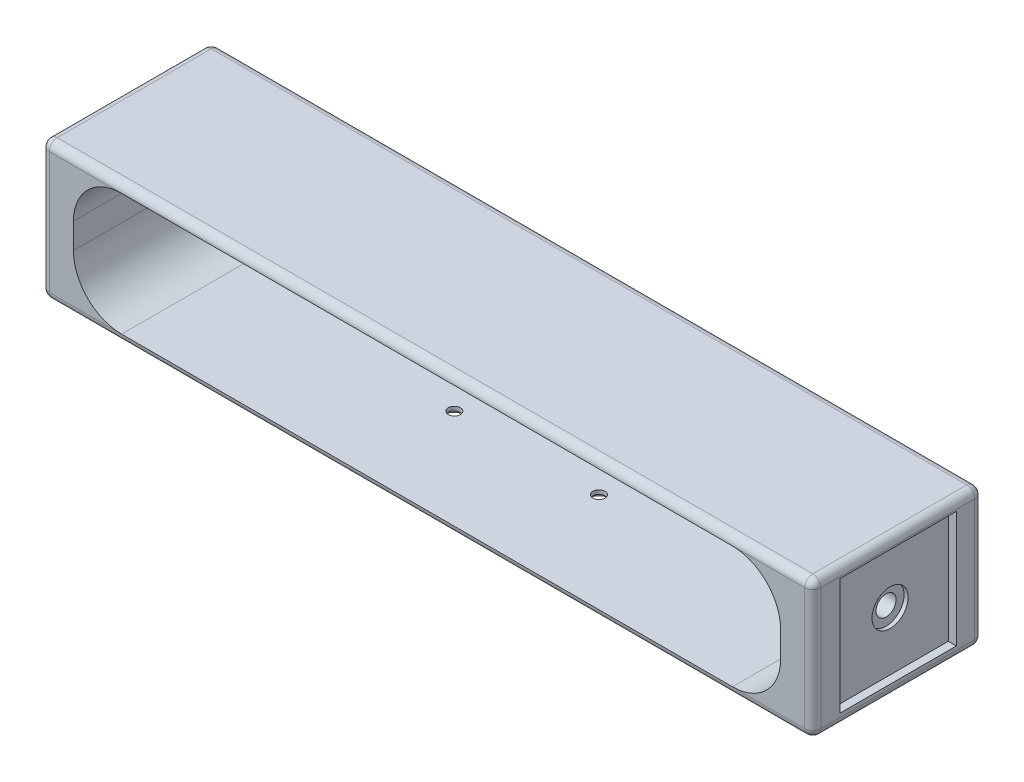
SolidWorks part; units mm, degrees
ref_plane "Front Plane" through (0, 0, 0) normal (0, 0, 1) x (1, 0, 0)
ref_plane "Top Plane" through (0, 0, 0) normal (0, 1, 0) x (1, 0, 0)
ref_plane "Right Plane" through (0, 0, 0) normal (1, 0, 0) x (0, 0, -1)
sketch "Sketch1" plane through (0, 0, 0) normal (0, 1, 0) x (1, 0, 0)
  line L1 (-96, 21.15) -> (96, 21.15)
  line L2 (-96, 21.15) -> (-96, -21.15)
  line L3 (-96, -21.15) -> (96, -21.15)
  line L4 (96, 21.15) -> (96, -21.15)
  line L5 (-96, 21.15) -> (96, -21.15) construction
  line L6 (-96, -21.15) -> (96, 21.15) construction
  point P0 (0, 0)
  dimension "D1" = 42.3
  dimension "D2" = 192
extrude "Boss-Extrude1" add sketch "Sketch1" along normal blind 2
sketch "Sketch2" plane through (0, 2, 0) normal (0, 1, 0) x (1, 0, 0)
  line L0 (-96, -21.15) -> (96, -21.15) construction
  line L1 (-96, -21.15) -> (-88, -21.15)
  line L2 (-96, -21.15) -> (-96, 21.15)
  line L3 (-96, 21.15) -> (-88, 21.15)
  line L4 (-88, -21.15) -> (-88, 21.15)
  line L5 (96, 21.15) -> (88, 21.15)
  line L6 (96, 21.15) -> (96, -21.15)
  line L7 (96, -21.15) -> (88, -21.15)
  line L8 (88, 21.15) -> (88, -21.15)
  line L10 (88, 21.15) -> (-88, 21.15)
  line L11 (88, 21.15) -> (88, 19.15)
  line L12 (88, 19.15) -> (-88, 19.15)
  line L13 (-88, 21.15) -> (-88, 19.15)
  line M5 (96, -21.15) -> (96, 21.15)
  line M6 (96, 21.15) -> (-96, 21.15)
  line M7 (-96, 21.15) -> (-96, -21.15)
  line M8 (-96, -21.15) -> (96, -21.15)
  dimension "D1" = 8
  dimension "D2" = 8
  dimension "D3" = 2
extrude "Boss-Extrude2" add sketch "Sketch2" along normal blind 30.35 contours L4 M8 M6 M7 | L12 L8 L4 M6 | L8 M6 M8 M5 region at (-92, 2, 0) region at (0, 2, -20.15) region at (92, 2, 0)
sketch "Sketch3" plane through (0, 32.35, 0) normal (0, 1, 0) x (1, 0, 0)
  line L1 (-96, 21.15) -> (96, 21.15)
  line L2 (-96, 21.15) -> (-96, -21.15)
  line L3 (-96, -21.15) -> (96, -21.15)
  line L4 (96, 21.15) -> (96, -21.15)
extrude "Boss-Extrude3" add sketch "Sketch3" along normal blind 2
fillet "Fillet1" radius 12 1 edges at (-88, 32.35, 1)
fillet "Fillet2" radius 12 1 edges at (-88, 2, 1)
fillet "Fillet3" radius 12 1 edges at (88, 32.35, 1)
fillet "Fillet4" radius 12 1 edges at (88, 2, 1)
sketch "Sketch4" plane through (0, 0, -19.15) normal (0, 0, 1) x (1, 0, 0)
  line L0 (-88, 20.35) -> (-88, 14)
  line L1 (-88, 14) -> (-76, 2)
  line L2 (-76, 2) -> (-26, 2)
  line L3 (76, 2) -> (-76, 2) construction
  line L4 (-26, 2) -> (-26, 32.35)
  line L5 (76, 32.35) -> (-76, 32.35) construction
  line L6 (-26, 32.35) -> (-76, 32.35)
  line L7 (-76, 32.35) -> (-88, 20.35)
  arc A0 (-76, 32.35) -> (-88, 20.35) centre (-76, 20.35) ccw
  arc A1 (-88, 14) -> (-76, 2) centre (-76, 14) ccw
  line M7 (-76, 2) -> (76, 2)
  line M11 (76, 32.35) -> (-76, 32.35)
  arc M12 (-76, 32.35) -> (-88, 20.35) centre (-76, 20.35) ccw
  line M13 (-88, 20.35) -> (-88, 14)
  arc M14 (-88, 14) -> (-76, 2) centre (-76, 14) ccw
  dimension "D1" = 50
  dimension "D2" = 50
extrude "Cut-Extrude1" cut sketch "Sketch4" against normal blind 2 contours L7 M12 | L1 M14 | L7 L1 L4 M11 M13 M7 region at (-54.7626, 17.175, -19.15) region at (-83.0078, 27.3578, -19.15) region at (-83.0078, 6.9922, -19.15)
sketch "Sketch5" plane through (0, 0, -19.15) normal (0, 0, 1) x (1, 0, 0)
  line L0 (76, 32.35) -> (26, 32.35)
  line L1 (76, 32.35) -> (-26, 32.35) construction
  line L2 (26, 32.35) -> (26, 2)
  line L3 (76, 2) -> (-26, 2) construction
  line L4 (26, 2) -> (76, 2)
  line L5 (76, 2) -> (88, 14)
  line L6 (88, 14) -> (88, 20.35)
  line L7 (88, 20.35) -> (76, 32.35)
  arc A0 (76, 2) -> (88, 14) centre (76, 14) ccw construction
  arc A1 (76, 32.35) -> (88, 20.35) centre (76, 20.35) cw
  arc A2 (88, 14) -> (76, 2) centre (76, 14) cw
  line M8 (-26, 2) -> (76, 2)
  arc M9 (76, 2) -> (88, 14) centre (76, 14) ccw
  line M10 (88, 14) -> (88, 20.35)
  arc M11 (88, 20.35) -> (76, 32.35) centre (76, 20.35) ccw
  line M12 (76, 32.35) -> (-26, 32.35)
  dimension "D1" = 50
extrude "Cut-Extrude2" cut sketch "Sketch5" against normal blind 2 contours L7 L2 L5 M10 M12 M8 | L7 M11 | L5 M9 region at (54.7626, 17.175, -19.15) region at (83.0078, 27.3578, -19.15) region at (83.0078, 6.9922, -19.15)
sketch "Sketch6" plane through (-96, 0, 0) normal (-1, 0, 0) x (0, 0, 1)
  circle A0 centre (0, 17.175) radius 4
extrude "Boss-Extrude5" add sketch "Sketch6" along normal blind 6
sketch "Sketch7" plane through (-102, 0, 0) normal (-1, 0, 0) x (0, 0, 1)
  circle A0 centre (0, 17.175) radius 2.25
  dimension "D1" = 4.5
extrude "Cut-Extrude3" cut sketch "Sketch7" against normal blind 10
sketch "Sketch8" plane through (-102, 0, 0) normal (-1, 0, 0) x (0, 0, 1)
  line L1 (-0.75, 21.7837) -> (0.75, 21.7837)
  line L2 (-0.75, 21.7837) -> (-0.75, 12.5663)
  line L3 (-0.75, 12.5663) -> (0.75, 12.5663)
  line L4 (0.75, 21.7837) -> (0.75, 12.5663)
  line L5 (-0.75, 21.7837) -> (0.75, 12.5663) construction
  line L6 (-0.75, 12.5663) -> (0.75, 21.7837) construction
  point P0 (0, 17.175)
  dimension "D1" = 1.5
extrude "Cut-Extrude4" cut sketch "Sketch8" against normal blind 6
sketch "Sketch10" plane through (0, 0, 0) normal (0, -1, 0) x (1, 0, 0)
  circle A0 centre (-18.0029, -3.6557) radius 1.5
  circle A1 centre (17.9971, -3.6557) radius 1.5
  dimension "D1" = 3
  dimension "D2" = 3
extrude "Cut-Extrude9" cut sketch "Sketch10" against normal blind 6
fillet "Fillet5" radius 2 1 edges at (0, 0, -21.15)
fillet "Fillet6" radius 2 1 edges at (0, 34.35, -21.15)
fillet "Fillet9" radius 2 5 edges at (96, 34.35, 1) (96, 33.7642, -20.5642) (96, 0, 1) (96, 0.5858, -20.5642) (96, 17.175, -21.15)
fillet "Fillet10" radius 2 5 edges at (-96, 34.35, 1) (-96, 33.7642, -20.5642) (-96, 0, 1) (-96, 0.5858, -20.5642) (-96, 17.175, -21.15)
fillet "Fillet11" radius 2 8 edges at (-95.4142, 33.7642, 21.15) (-96, 17.175, 21.15) (-95.4142, 0.5858, 21.15) (0, 0, 21.15) (95.4142, 0.5858, 21.15) (96, 17.175, 21.15) (95.4142, 33.7642, 21.15) (0, 34.35, 21.15)
fillet "Fillet14" radius 1 1 edges at (-102, 17.175, 4)
fillet "Fillet15" radius 1 1 edges at (-102, 17.175, -4)
sketch "Sketch11" plane through (0, 0, 0) normal (0, -1, 0) x (-1, 0, 0)
  circle A0 centre (18.0029, 3.6557) radius 2.5
  circle A1 centre (-17.9971, 3.6557) radius 2.5
  dimension "D1" = 5
  dimension "D2" = 5
extrude "Cut-Extrude11" cut sketch "Sketch11" against normal blind 1
sketch "Sketch12" plane through (96, 0, 0) normal (1, 0, 0) x (0, 0, -1)
  circle A0 centre (0.0908, 17.4324) radius 4.5
  dimension "D1" = 9
extrude "Cut-Extrude12" cut sketch "Sketch12" against normal blind 1
sketch "Sketch13" plane through (96, 0, 0) normal (1, 0, 0) x (0, 0, -1)
  circle A0 centre (0.0908, 17.4324) radius 2.5
  dimension "D1" = 5
extrude "Cut-Extrude14" cut sketch "Sketch13" against normal blind 10
sketch "Sketch14" plane through (96, 0, 0) normal (1, 0, 0) x (0, 0, -1)
  line L1 (-14.4092, 31.9324) -> (14.5908, 31.9324)
  line L2 (-14.4092, 31.9324) -> (-14.4092, 2.9324)
  line L3 (-14.4092, 2.9324) -> (14.5908, 2.9324)
  line L4 (14.5908, 31.9324) -> (14.5908, 2.9324)
  line L5 (-14.4092, 31.9324) -> (14.5908, 2.9324) construction
  line L6 (-14.4092, 2.9324) -> (14.5908, 31.9324) construction
  point P0 (0.0908, 17.4324)
  dimension "D1" = 29
  dimension "D2" = 29
extrude "Cut-Extrude15" cut sketch "Sketch14" against normal blind 2
sketch "Sketch15" plane through (94, 0, 0) normal (1, 0, 0) x (0, 0, -1)
  circle A0 centre (0.0908, 17.4324) radius 4.5
  dimension "D1" = 9
extrude "Cut-Extrude16" cut sketch "Sketch15" against normal blind 1
fillet "Fillet16" radius 0.5 1 edges at (-102, 17.175, 2.25)
fillet "Fillet17" radius 0.5 1 edges at (-102, 17.175, -2.25)
sketch "Sketch16" plane through (0, 0, -21.15) normal (0, 0, -1) x (-1, 0, 0)
  line L0 (-26, 2) -> (26, 2) construction
  line L1 (-26, 32.35) -> (-18, 32.35)
  line L2 (-26, 32.35) -> (-26, 2)
  line L3 (-26, 2) -> (-18, 2)
  line L4 (-18, 32.35) -> (-18, 2)
  line L6 (26, 32.35) -> (18, 32.35)
  line L7 (26, 32.35) -> (26, 2)
  line L8 (26, 2) -> (18, 2)
  line L9 (18, 32.35) -> (18, 2)
  dimension "D1" = 8
  dimension "D2" = 8
extrude "Cut-Extrude17" cut sketch "Sketch16" against normal blind 80
fillet "Fillet18" radius 2 1 edges at (-18, 17.175, -21.15)
fillet "Fillet19" radius 2 1 edges at (18, 17.175, -21.15)
